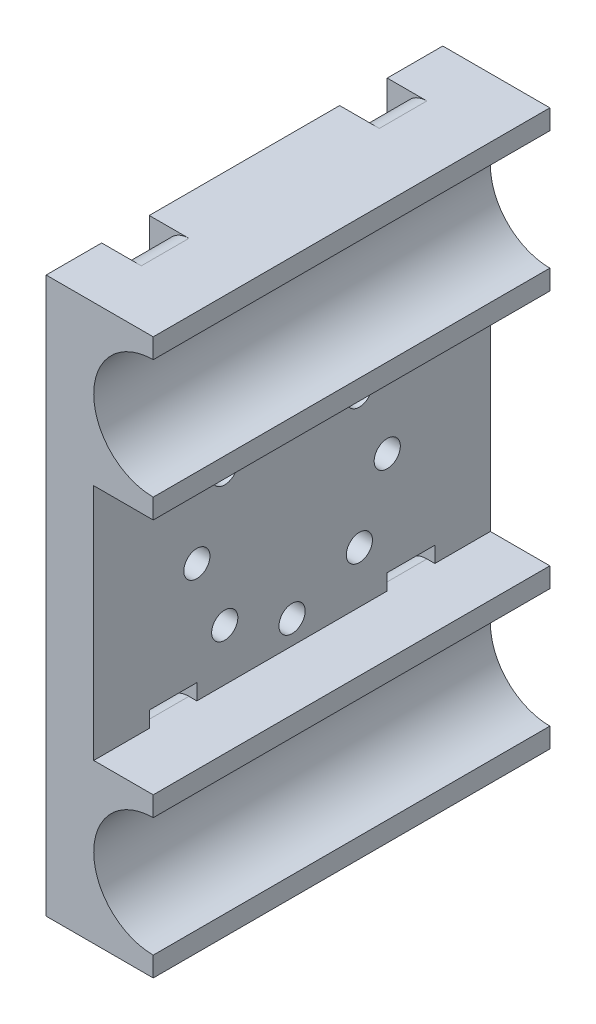
SolidWorks part; units mm, degrees
ref_plane "Plano frontal" through (0, 0, 0) normal (0, 0, 1) x (1, 0, 0)
ref_plane "Plano superior" through (0, 0, 0) normal (0, 1, 0) x (1, 0, 0)
ref_plane "Plano direito" through (0, 0, 0) normal (1, 0, 0) x (0, 0, -1)
sketch "Esboço1" plane through (0, 0, 0) normal (0, 0, 1) x (1, 0, 0)
  line L0 (0, 0) -> (67.7245, 0) construction
  line L1 (0, 35) -> (0, -35)
  line L2 (0, -35) -> (13.5, -35)
  line L3 (13.5, -35) -> (13.5, -32.5)
  line L4 (13.5, -17.5) -> (13.5, -15)
  line L5 (13.5, -15) -> (6, -15)
  line L6 (6, -15) -> (6, 15)
  line L7 (6, 15) -> (13.5, 15)
  line L8 (13.5, 15) -> (13.5, 17.5)
  line L9 (13.5, 32.5) -> (13.5, 35)
  line L10 (13.5, 35) -> (0, 35)
  arc A0 (13.5, 32.5) -> (13.5, 17.5) centre (13.5, 25) ccw
  arc A1 (13.5, -17.5) -> (13.5, -32.5) centre (13.5, -25) ccw
  point P3 (0, 0)
  dimension "D1" = 15
  dimension "D2" = 50
  dimension "D3" = 6
  dimension "D4" = 70
extrude "Ressalto-extrusão1" add sketch "Esboço1" along normal blind 50
sketch "Esboço2" plane through (6, 0, 0) normal (1, 0, 0) x (0, 0, -1)
  line L1 (-25, 15) -> (-25, -15) construction
  line L2 (-50, -15) -> (0, -15) construction
  line L3 (0, 0) -> (-50, 0) construction
  line L4 (-50, -15) -> (-50, 15) construction
  line L5 (-43, 15) -> (-37, 13) construction
  line L6 (-43, 13) -> (-37, 15) construction
  line L7 (-50, 15) -> (0, 15) construction
  line L8 (-7, 13) -> (-13, 13)
  line L9 (-7, 13) -> (-7, 15)
  line L10 (-7, 15) -> (-13, 15)
  line L11 (-13, 13) -> (-13, 15)
  line L12 (-7, 13) -> (-13, 15) construction
  line L13 (-7, 15) -> (-13, 13) construction
  line L15 (-37, 13) -> (-37, 15)
  line L16 (-43, 15) -> (-37, 15)
  line L17 (-43, 13) -> (-43, 15)
  line L18 (-43, 13) -> (-37, 13)
  line L19 (-7, -15) -> (-13, -13) construction
  line L20 (-7, -13) -> (-13, -15) construction
  line L21 (-43, -13) -> (-37, -15) construction
  line L22 (-43, -15) -> (-37, -13) construction
  line L23 (-43, -13) -> (-37, -13)
  line L24 (-43, -13) -> (-43, -15)
  line L25 (-43, -15) -> (-37, -15)
  line L26 (-37, -13) -> (-37, -15)
  line L27 (-13, -13) -> (-13, -15)
  line L28 (-7, -15) -> (-13, -15)
  line L29 (-7, -13) -> (-7, -15)
  line L30 (-7, -13) -> (-13, -13)
  line L31 (0, -15) -> (0, 15) construction
  circle A0 centre (-25, 12) radius 1.65
  circle A1 centre (-16.5147, 8.4853) radius 1.65
  circle A2 centre (-13, 0) radius 1.65
  circle A3 centre (-16.5147, -8.4853) radius 1.65
  circle A4 centre (-25, -12) radius 1.65
  circle A5 centre (-33.4853, -8.4853) radius 1.65
  circle A6 centre (-37, 0) radius 1.65
  circle A7 centre (-33.4853, 8.4853) radius 1.65
  point P7 (-10, 14)
  point P19 (-40, 14)
  point P29 (-40, -14)
  point P30 (-10, -14)
  point P35 (-25, 0)
  point P36 (0, 0)
  point P37 (-20.434, -2.9085)
  point P38 (0, 0)
  point P53 (-25, 0)
  point P54 (-35.0907, 10.0907)
  point P55 (0, 0)
  dimension "D4" = 3.3
  dimension "D1" = 6
  dimension "D2" = 2
  dimension "D3" = 10
  dimension "D5" = 12
  dimension "D6" = 8
extrude "Corte-extrusão1" cut sketch "Esboço2" against normal blind 10
sketch "Esboço3" plane through (0, 0, 0) normal (-1, 0, 0) x (0, 0, 1)
  line L0 (50, 35) -> (0, 35) construction
  line L1 (13, 15) -> (7, 15)
  line L2 (13, 15) -> (13, 35)
  line L3 (13, 35) -> (7, 35)
  line L4 (7, 15) -> (7, 35)
  line L5 (25, 35) -> (25, -35) construction
  line L6 (50, -35) -> (0, -35) construction
  line L7 (0, 0) -> (50, 0) construction
  line L8 (50, 35) -> (50, -35) construction
  line L9 (43, 15) -> (43, 35)
  line L10 (37, 35) -> (43, 35)
  line L11 (37, 15) -> (37, 35)
  line L12 (37, 15) -> (43, 15)
  line L13 (37, -15) -> (43, -15)
  line L14 (37, -15) -> (37, -35)
  line L15 (37, -35) -> (43, -35)
  line L16 (43, -15) -> (43, -35)
  line L17 (7, -15) -> (7, -35)
  line L18 (13, -35) -> (7, -35)
  line L19 (13, -15) -> (13, -35)
  line L20 (13, -15) -> (7, -15)
extrude "Corte-extrusão2" cut sketch "Esboço3" against normal blind 2
fillet "Filete1" radius 3 8 edges at (2, -35, 10) (2, -35, 40) (2, 35, 40) (2, 35, 10) (2, -15, 10) (2, -15, 40) (2, 15, 40) (2, 15, 10)
sketch "Esboço4" plane through (6, 0, 0) normal (1, 0, 0) x (0, 0, -1)
  line L0 (0, -15) -> (0, 15) construction
  line L1 (0, -3.75) -> (-6.6629, -3.75)
  line L2 (0, -3.75) -> (0, -9.75)
  line L3 (0, -9.75) -> (-6.6629, -9.75)
  line L4 (-6.6629, -3.75) -> (-6.6629, -9.75)
  line L5 (0, 0) -> (-50, 0) construction
  line L6 (0, 3.75) -> (-6.6629, 3.75)
  line L7 (0, 3.75) -> (0, 9.75)
  line L8 (0, 9.75) -> (-6.6629, 9.75)
  line L9 (-6.6629, 3.75) -> (-6.6629, 9.75)
  line L10 (-50, -15) -> (-50, 15) construction
  dimension "D1" = 13.5
  dimension "D2" = 6
